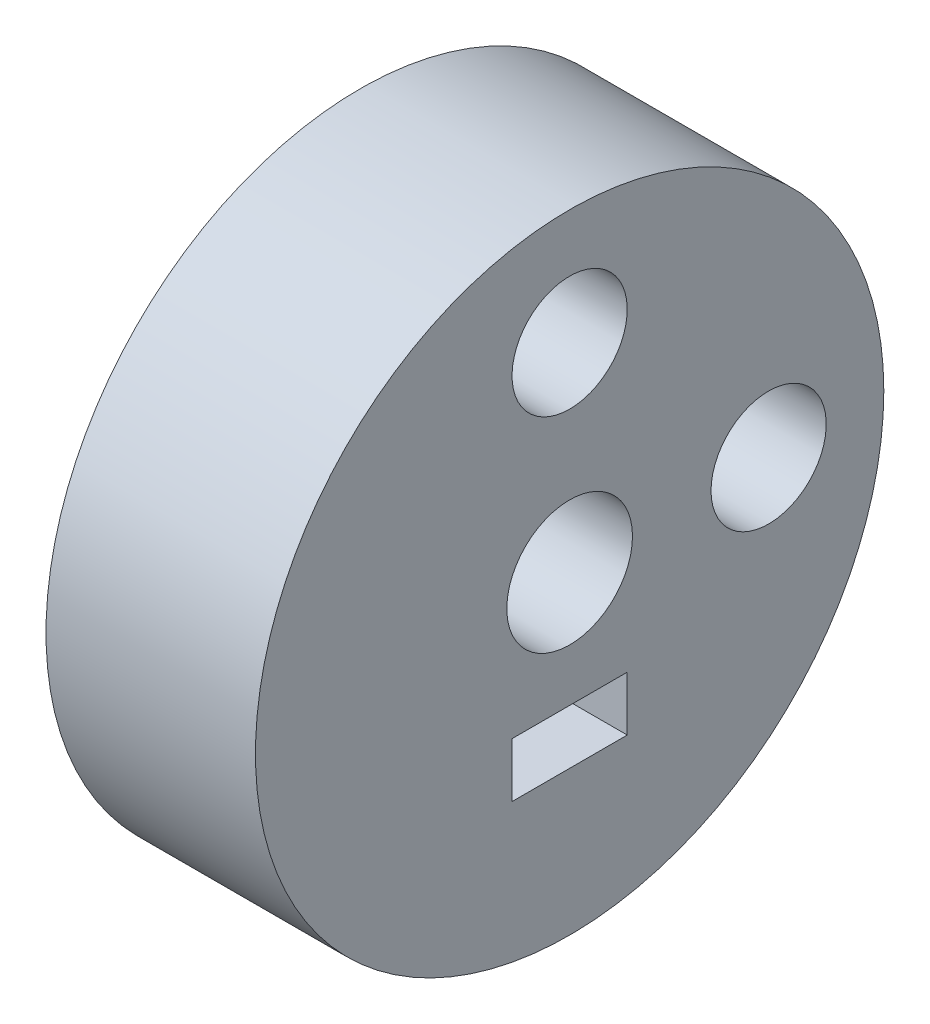
SolidWorks part; units mm, degrees
ref_plane "Alzado" through (0, 0, 0) normal (0, 0, 1) x (1, 0, 0)
ref_plane "Planta" through (0, 0, 0) normal (0, 1, 0) x (1, 0, 0)
ref_plane "Vista lateral" through (0, 0, 0) normal (1, 0, 0) x (0, 0, -1)
sketch "Croquis2" plane through (0, 0, 0) normal (1, 0, 0) x (0, 0, -1)
  circle A0 centre (0, 0) radius 15
  circle A2 centre (0, 0) radius 3
  dimension "D1" = 30
  dimension "D2" = 6
extrude "Saliente-Extruir1" add sketch "Croquis2" against normal blind 10
sketch "Croquis3" plane through (0, 0, 0) normal (0, 1, 0) x (1, 0, 0)
  line L0 (0, 0) -> (-10, 0) construction
  line L2 (-10, 15) -> (-10, -15) construction
  circle A0 centre (-5, 0) radius 1.5
  dimension "D1" = 3
extrude "Cortar-Extruir1" cut sketch "Croquis3" against normal through all
sketch "Croquis6" plane through (0, 0, 0) normal (1, 0, 0) x (0, 0, -1)
  line L2 (2.75, -8.1) -> (-2.75, -8.1)
  line L3 (2.75, -8.1) -> (2.75, -5.5)
  line L4 (2.75, -5.5) -> (-2.75, -5.5)
  line L5 (-2.75, -8.1) -> (-2.75, -5.5)
  line L6 (2.75, -8.1) -> (-2.75, -5.5) construction
  line L7 (2.75, -5.5) -> (-2.75, -8.1) construction
  circle A2 centre (0, 0) radius 3 construction
  point P0 (0, -3)
  point P4 (0, -5.5)
  point P7 (0, -6.8)
  dimension "D1" = 5.5
  dimension "D2" = 2.6
  dimension "D3" = 2.5
extrude "Cortar-Extruir2" cut sketch "Croquis6" against normal through all
sketch "Croquis7" plane through (0, 0, 0) normal (0, 1, 0) x (1, 0, 0)
  circle A0 centre (-5, 0) radius 2.75
  dimension "D1" = 5.5
extrude "Cortar-Extruir3" cut sketch "Croquis7" against normal through all from offset 11.5 offset against normal yes
sketch "Croquis9" plane through (0, 0, 0) normal (1, 0, 0) x (0, 0, -1)
  circle A0 centre (0, 0) radius 9.5 construction
  circle A1 centre (9.5, 0) radius 1.5
  dimension "D1" = 19
  dimension "D2" = 3
extrude "Cortar-Extruir4" cut sketch "Croquis9" against normal through all
sketch "Croquis11" plane through (-10, 0, 0) normal (-1, 0, 0) x (0, 0, 1)
  circle A0 centre (-9.5, 0) radius 2.75
  dimension "D1" = 5.5
extrude "Cortar-Extruir5" cut sketch "Croquis11" against normal through all from offset 2 offset against normal yes
ref_axis "Eje1" through (0.4, 0, 0) along (-1, 0, 0)
ref_plane "Plano1" through (0, 0, 0) normal (0, 0.7071, 0.7071) x (-1, 0, 0)
mirror "Simetría1" about plane through (0, 0, 0) normal (0, 0.7071, 0.7071) of "Cortar-Extruir4", "Cortar-Extruir5"
